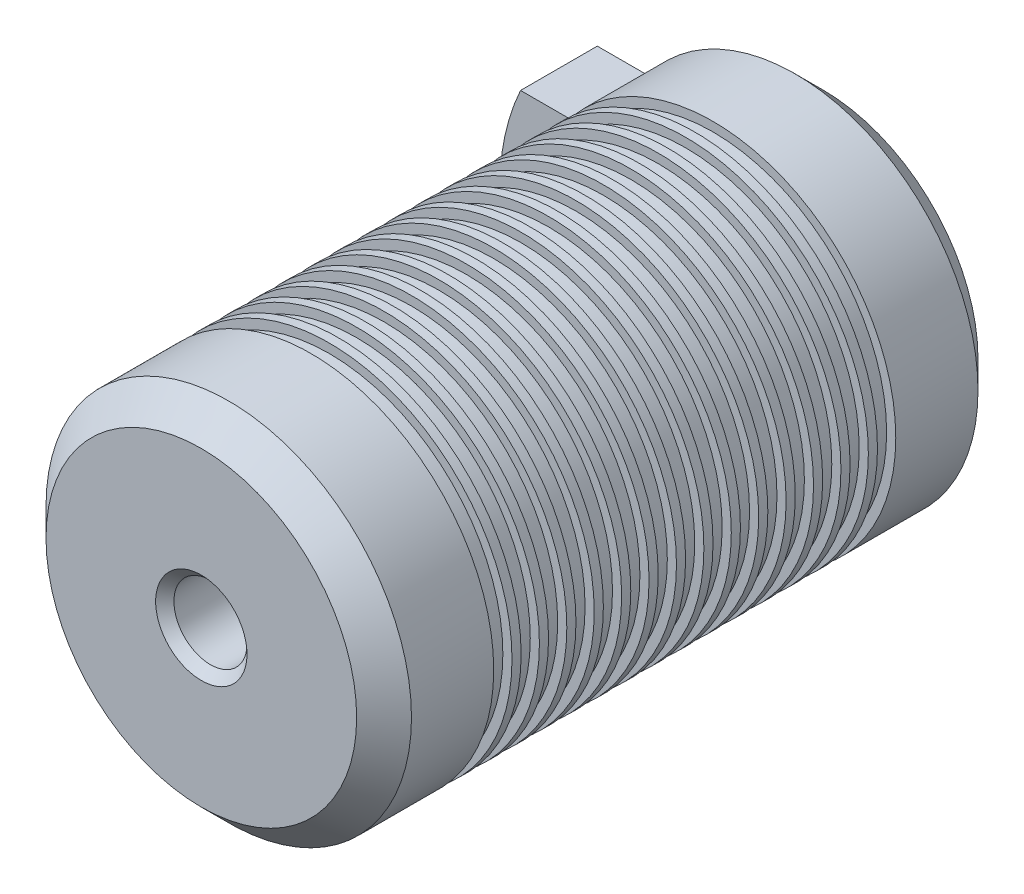
SolidWorks part; units mm, degrees
material "6061-T6 (SS)"
ref_plane "Front Plane" through (0, 0, 0) normal (0, 0, 1) x (1, 0, 0)
ref_plane "Top Plane" through (0, 0, 0) normal (0, 1, 0) x (1, 0, 0)
ref_plane "Right Plane" through (0, 0, 0) normal (1, 0, 0) x (0, 0, -1)
sketch "Sketch1" plane through (0, 0, 0) normal (0, 0, 1) x (1, 0, 0)
  circle A0 centre (0, 0) radius 20
  dimension "D1" = 40
extrude "Boss-Extrude1" add sketch "Sketch1" along normal blind 68
sketch "Sketch2" plane through (0, 0, 68) normal (0, 0, 1) x (1, 0, 0)
  circle A0 centre (0, 0) radius 2.5 construction
  circle A1 centre (0, 0) radius 4
  dimension "D1" = 5
  dimension "D2" = 1.5
extrude "Cut-Extrude1" cut sketch "Sketch2" against normal blind 10
chamfer "Chamfer1" distance 3 angle 45 2 edges at (20, 0, 0) (20, 0, 68)
sketch3d "3DSketch1"
  line L0 (0, 0, 68) -> (0, 0, 0)
  circle A0 centre (0, 0, 0) radius 17 construction
  circle A1 centre (0, 0, 68) radius 17 construction
  circle A2 centre (0, 0, 0) radius 17
  circle A3 centre (0, 0, 68) radius 17
  point P2 (0, 0, -17)
  point P5 (0, 0, 85)
  point P7 (0, 0, -17)
  point P9 (0, 0, 85)
sketch "Sketch5" plane through (0, 0, 68) normal (0, 0, 1) x (1, 0, 0)
  circle A0 centre (0, 0) radius 19
  circle A1 centre (0, 0) radius 20 construction
  circle A2 centre (0, 0) radius 20
  dimension "D1" = 1
extrude "Cut-Extrude3" cut sketch "Sketch5" against normal blind 2 from offset 12 offset against normal yes
pattern_linear "LPattern1" count 15 spacing 3 along (0, 0, -1) of "Cut-Extrude3"
chamfer "Chamfer2" distance 1 angle 45 1 edges at (4, 0, 68)
sketch3d "3DSketch2" plane through (0, 0, 0) normal (0, 0, 1) x (1, 0, 0)
sketch "Sketch6" plane through (-20, 0, 0) normal (-1, 0, 0) x (0, 0, 1)
  line L0 (12, -19) -> (12, 19) construction
  line L2 (12, -19) -> (12, 19)
  line L3 (1.7, 20) -> (1.7, -20)
  line L4 (0, 17) -> (0, -17) construction
  line L5 (0, 17) -> (0, -17)
  line L6 (1.7, 10.5) -> (10.1, 10.5)
  line L7 (10.1, 10.5) -> (10.1, -10.5)
  line L8 (10.1, -10.5) -> (1.7, -10.5)
  line L9 (0, 0) -> (10.1, 0) construction
  point P12 (11.4, 0)
  dimension "D1" = 8.4
  dimension "D2" = 21
  dimension "D3" = 1.7
extrude "Boss-Extrude2" add sketch "Sketch6" against normal up to surface and the other way blind 5.5 contours L3 L9 L7 L6 | L9 L3 L8 L7 region at (-20, 5.25, 5.9) region at (-20, -5.25, 5.9) up to face at (20, 0, 3)
sketch "Sketch7" plane through (0, 0, 0) normal (0, 0, 1) x (1, 0, 0)
  line L0 (-25.5, 10.5) -> (-25.5, -10.5) construction
  line L1 (-25.5, 10.5) -> (-25.5, -10.5)
  line L2 (-25.5, 10.5) -> (-22.9633, 10.5)
  line L3 (-25.5, -10.5) -> (-22.9633, -10.5)
  line L4 (-25.5, 0) -> (-25.25, 0)
  circle A0 centre (0, 0) radius 25.25
  point P5 (-25.5, 0)
  point P6 (-25.25, 0)
  dimension "D1" = 0.25
extrude "Cut-Extrude4" cut sketch "Sketch7" along normal up to surface (10.1 mm away) contours A0 L2 L1 L4 | A0 L4 L1 L3 region at (-24.7714, 7.2356, 0) region at (-24.7714, -7.2356, 0) up to face at (-22.0055, 0, 10.1)
